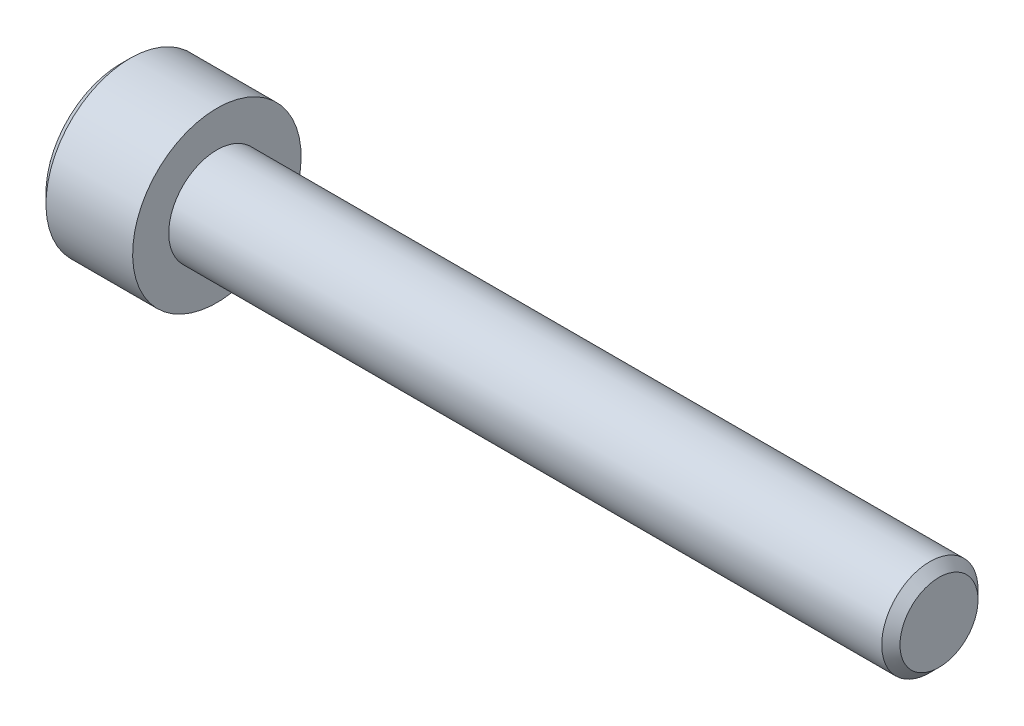
SolidWorks part; units mm, degrees
ref_plane "Front Plane" through (0, 0, 0) normal (0, 0, 1) x (1, 0, 0)
ref_plane "Top Plane" through (0, 0, 0) normal (0, 1, 0) x (1, 0, 0)
ref_plane "Right Plane" through (0, 0, 0) normal (1, 0, 0) x (0, 0, -1)
ref_axis "Axis_X" through (-5.7, 0, 0) along (1, 0, 0)
ref_axis "Axis_Y" through (0, 3.85, 0) along (0, -1, 0)
ref_axis "Axis_Z" through (0, 0, -3.85) along (0, 0, 1)
sketch "Sketch1" plane through (0, 0, 0) normal (0, 0, 1) x (1, 0, 0)
  line L0 (-4.1583, 0) -> (30, 0) construction
  line L1 (0, 2) -> (0, 3.5)
  line L2 (-4, 0) -> (-4, 3.1)
  line L3 (0, 2) -> (29.621, 2)
  line L4 (29.621, 2) -> (30, 1.621)
  line L5 (30, 1.621) -> (30, 0)
  line L6 (30, 0) -> (-4, 0)
  line L7 (-3.6, 3.5) -> (0, 3.5)
  line L8 (29.621, -2) -> (30, -1.621) construction
  line L9 (3.85, 0) -> (-3.85, 0) construction
  line L10 (-4, 3.1) -> (-3.6, 3.5)
  line L11 (-4, -3.1) -> (-3.6, -3.5) construction
  line L12 (0, -3.85) -> (0, 3.85) construction
  dimension "FIX_1" = 45
  dimension "M" = 4
  dimension "ATD_1" = 3.242
  dimension "L" = 30
  dimension "E" = 4
  dimension "A" = 7
revolve "Revolve1" add sketch "Sketch1" angle 360 about L6
sketch "Sketch2" plane through (-4, 0, 0) normal (-1, 0, 0) x (0, 0, 1)
  line L0 (0, -3.85) -> (0, 3.85) construction
  line L1 (0, 1.7321) -> (-1.5, 0.866)
  line L2 (-1.5, 0.866) -> (-1.5, -0.866)
  line L3 (-1.5, -0.866) -> (0, -1.7321)
  line L4 (0, -1.7321) -> (1.5, -0.866)
  line L5 (1.5, -0.866) -> (1.5, 0.866)
  line L6 (1.5, 0.866) -> (0, 1.7321)
  circle A0 centre (0, 0) radius 1.5 construction
  dimension "B" = 3
extrude "Cut-Extrude1" cut sketch "Sketch2" against normal blind 2
equation "\"Factor\"= 1.082532"
equation "\"Pitch\"= IIF ( \"M\" = 30 , 3.5 , IIF ( \"M\" = 24 , 3 , IIF ( \"M\" = 20 , 2.5 , IIF ( \"M\" = 16 , 2 , IIF ( \"M\" = 14 , 2 , IIF ( \"M\" = 12 , 1.75 , IIF ( \"M\" = 10 , 1.5 , IIF ( \"M\" = 8 , 1.25 , IIF ( \"M\" = 6 , 1 , IIF ( \"M\" = 5 , 0.8 , IIF ( \"M\" = 4 , 0.7 , IIF ( \"M\" = 3 , 0.5 , IIF ( \"M\" = 2.5 , 0.45 , 0.4 ) ) ) ) ) ) ) ) ) ) ) ) )"
equation "\"ATD_1\"= round ( \"M\" - \"Factor\" * \"Pitch\" , 3 )"
equation "\"L_s\"= IIF ( ( \"M\" = 12 and \"L\" > 50 ) , 36 , IIF ( ( \"M\" = 12 and \"L\" = < 50 ) , \"L\" , IIF ( ( \"M\" = 10 and \"L\" > 40 ) , 32 , IIF ( ( \"M\" = 10 and \"L\" = < 40 ) , \"L\" , IIF ( ( \"M\" = 8 and \"L\" > 35 ) , 28 , IIF ( ( \"M\" = 8 and \"L\" = < 35 ) , \"L\" , IIF ( ( \"M\" = 6 and \"L\" > 30 ) , 24 , IIF ( ( \"M\" = 6 and \"L\" = < 30 ) , \"L\" , IIF ( ( \"M\" = 5 and \"L\" > 25 ) , 22 , IIF ( ( \"M\" = 5 and \"L\" = < 25 ) , \"L\" , IIF ( ( \"M\" = 4 and \"L\" > 25 ) , 20 , IIF ( ( \"M\" = 4 and \"L\" = < 25 ) , \"L\" , IIF ( ( \"M\" = 3 and \"L\" > 20 ) , 18 , \"L\" ) ) ) ) ) ) ) ) ) ) ) ) )"
equation "\"E\"= \"M\""
equation "\"A\"= IIF ( \"M\" = 12 , 18 , IIF ( \"M\" = 10 , 16 , IIF ( \"M\" = 8 , 13 , IIF ( \"M\" = 6 , 10 , IIF ( \"M\" = 5 , 8.5 , IIF ( \"M\" = 4 , 7 , 5.5 ) ) ) ) ) )"
equation "\"B\"= IIF ( \"M\" = 12 , 10 , IIF ( \"M\" = 10 , 8 , IIF ( \"M\" = 8 , 6 , IIF ( \"M\" = 6 , 5 , IIF ( \"M\" = 5 , 4 , IIF ( \"M\" = 4 , 3 , 2.5 ) ) ) ) ) )"
equation "\"KSS_1\"= \"M\" / 10"
equation "\"KSS_2\"= \"M\" / 2"
